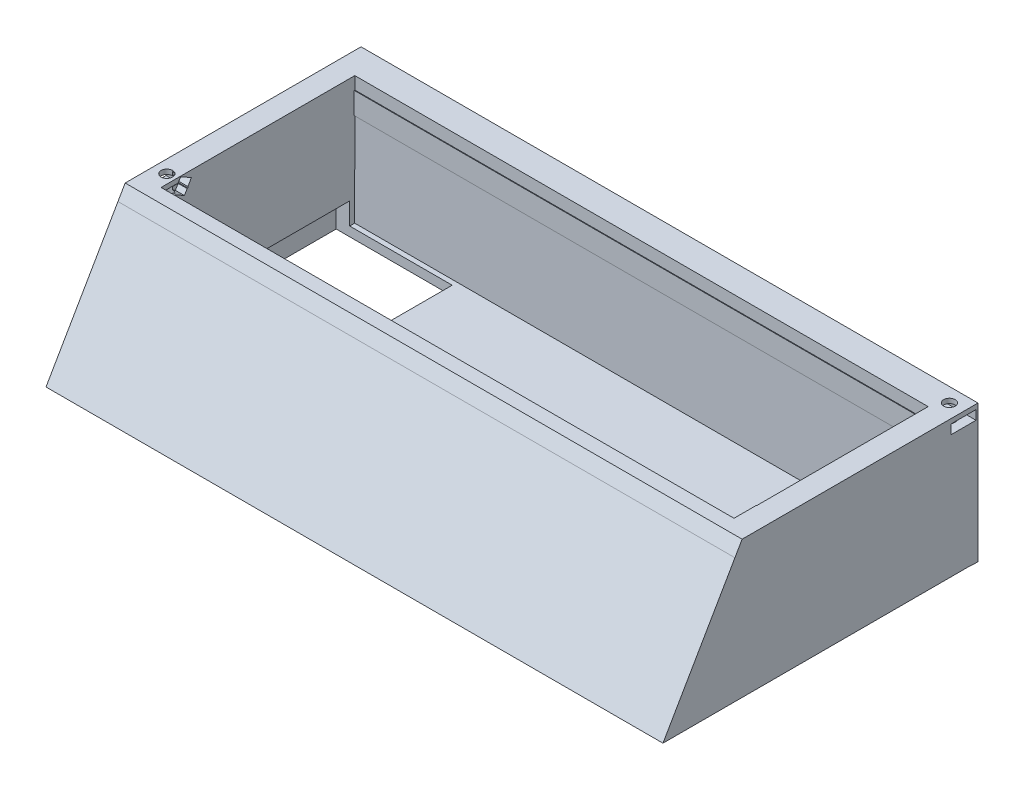
SolidWorks part; units mm, degrees
ref_plane "Alzado" through (0, 0, 0) normal (0, 0, 1) x (1, 0, 0)
ref_plane "Planta" through (0, 0, 0) normal (0, 1, 0) x (1, 0, 0)
ref_plane "Vista lateral" through (0, 0, 0) normal (1, 0, 0) x (0, 0, -1)
sketch "Sketch1" plane through (0, 0, 0) normal (1, 0, 0) x (0, 0, -1)
  line L0 (22.1085, 0) -> (32.4418, 17.8992)
  line L3 (-73.8644, -51.971) -> (121.1356, -51.9647) construction
  line L4 (22.1085, 0) -> (121.18, 0)
  line L5 (121.18, 0) -> (121.2142, 40)
  line L6 (45.2007, 40) -> (121.2142, 40)
  line L7 (32.4418, 17.8992) -> (45.2007, 40)
  line L8 (121.1416, -44.9647) -> (121.18, 0) construction
  dimension "D1" = 120
  dimension "D2" = 40
  dimension "D3" = 120
  dimension "D4" = 76.0135
extrude "Boss-Extrude1" add sketch "Sketch1" along normal blind 198
shell "Shell1" thickness 7 removed face at (99, 0, -71.6442)
sketch "Sketch2" plane through (0, 0, 0) normal (-1, 0, 0) x (0, 0, 1)
  line L0 (-30.1912, 0) -> (-32.9749, 0)
  line L1 (-32.9749, 0) -> (-52.026, 33)
  line L2 (73.8644, -51.971) -> (-121.1356, -51.9647) construction
  line L3 (-52.026, 33) -> (-49.2423, 33)
  line L4 (-49.2423, 33) -> (-30.1912, 0)
  dimension "D1" = 120
extrude "Boss-Extrude2" add sketch "Sketch2" against normal blind 191
ref_plane "Plane1" through (99, 0, 0) normal (1, 0, 0) x (0, 0, -1)
sketch "Sketch6" plane through (0, -0.1036, -121.1799) normal (0, -0.0009, -1) x (-1, 0, 0)
  line L1 (-198, 40.1036) -> (0, 40.1036)
  line L2 (-198, 40.1036) -> (-198, 0)
  line L3 (-198, 0) -> (0, 0)
  line L4 (0, 40.1036) -> (0, 0)
extrude "Boss-Extrude4" add sketch "Sketch6" along normal blind 2
sketch "Sketch7" plane through (0, 0, 0) normal (-1, 0, 0) x (0, 0, 1)
  line L1 (-123.1877, 9.047) -> (-35.2379, 9.047)
  line L2 (-123.1877, 9.047) -> (-123.1877, 12.047)
  line L3 (-123.1877, 12.047) -> (-35.2379, 12.047)
  line L4 (-35.2379, 9.047) -> (-35.2379, 12.047)
  dimension "D1" = 3
  dimension "D2" = 87.9498
  dimension "D3" = 3
ref_plane "Plane3" through (0, -0.0976, -114.1799) normal (0, 0.0009, 1) x (1, 0, 0)
ref_plane "Plane4" through (0, -14.278, -24.7321) normal (0, -0.5, -0.866) x (-1, 0, 0)
ref_plane "Plane5" through (7, 0, 0) normal (1, 0, 0) x (0, 0, -1)
ref_plane "Plane6" through (191, 0, 0) normal (-1, 0, 0) x (0, 0, 1)
sketch "Sketch8" plane through (198, 0, 0) normal (1, 0, 0) x (0, 0, -1)
  line L0 (123.2142, 39.9983) -> (123.2142, 52.0483)
  line L1 (123.2142, 39.9983) -> (45.2007, 40)
  line L2 (45.2007, 40) -> (52.1572, 52.0483)
  line L3 (123.2142, 52.0483) -> (52.1572, 52.0483)
  dimension "D1" = 12.05
  dimension "D2" = 78.0135
extrude "Boss-Extrude6" add sketch "Sketch8" against normal blind 198
sketch "Sketch9" plane through (0, 40.001, -0.0009) normal (0, -1, 0) x (-1, 0, 0)
  line L0 (0, 52.156) -> (-198, 52.156) construction
  line L1 (-7, 114.2131) -> (-191, 114.2131)
  line L2 (-7, 114.2131) -> (-7, 59.156)
  line L3 (-7, 59.156) -> (-191, 59.156)
  line L4 (-191, 114.2131) -> (-191, 59.156)
  line L5 (0, 123.2131) -> (0, 52.156) construction
  line L6 (0, 123.2131) -> (-198, 123.2131) construction
  line L7 (-198, 123.2131) -> (-198, 52.156) construction
  dimension "D1" = 7
  dimension "D2" = 7
  dimension "D3" = 9
  dimension "D4" = 7
extrude "Cut-Extrude1" cut sketch "Sketch9" against normal blind 4
sketch "Sketch10" plane through (0, -14.278, -24.7321) normal (0, -0.5, -0.866) x (-1, 0, 0)
  line L1 (-195.105, 67.1286) -> (-4.105, 67.1286)
  line L2 (-195.105, 67.1286) -> (-195.105, 62.6734)
  line L3 (-195.105, 62.6734) -> (-4.105, 62.6734)
  line L4 (-4.105, 67.1286) -> (-4.105, 62.6734)
  dimension "D1" = 191
  dimension "D2" = 191
extrude "Cut-Extrude2" cut sketch "Sketch10" along normal blind 4
ref_plane "Plane7" through (0, 44.001, -0.001) normal (0, -1, 0) x (-1, 0, 0)
split "Split4" trim tools "Plane7" bodies to split 114 resulting bodies 121
sketch "Sketch11" plane through (0, 44.001, -0.001) normal (0, 1, 0) x (1, 0, 0)
  circle A0 centre (4.1226, 56.7722) radius 1.8459
  circle A1 centre (193.3782, 118.6596) radius 1.8365
extrude "Cut-Extrude3" cut sketch "Sketch11" against normal blind 10
sketch "Sketch13" plane through (0, 0, 0) normal (-1, 0, 0) x (0, 0, 1)
  line L0 (-47.5102, 43.9999) -> (-123.2142, 43.9983) construction
  line L1 (-60.6515, 42.4996) -> (-52.6515, 42.4998)
  line L2 (-60.6515, 42.4996) -> (-60.6515, 39.4996)
  line L3 (-60.6515, 39.4996) -> (-52.6515, 39.4998)
  line L4 (-52.6515, 42.4998) -> (-52.6515, 39.4998)
  dimension "D1" = 8
  dimension "D2" = 3
  dimension "D3" = 3
  dimension "D4" = 1.5
extrude "Cut-Extrude4" cut sketch "Sketch13" against normal blind 10
sketch "Sketch15" plane through (198, 0, 0) normal (1, 0, 0) x (0, 0, -1)
  line L1 (122.5785, 42.4983) -> (114.5785, 42.4985)
  line L2 (122.5785, 42.4983) -> (122.5785, 39.5153)
  line L3 (122.5785, 39.5153) -> (114.5785, 39.5153)
  line L4 (114.5785, 42.4985) -> (114.5785, 39.5153)
  line L6 (47.5102, 43.9999) -> (123.2142, 43.9983) construction
  dimension "D1" = 1.5
  dimension "D2" = 8
extrude "Cut-Extrude6" cut sketch "Sketch15" against normal blind 10
sketch "Sketch16" plane through (0, 33, 0) normal (0, -1, 0) x (-1, 0, 0)
  line L1 (-7, 52.026) -> (-190.8842, 52.026)
  line L2 (-7, 52.026) -> (-7, 114.0066)
  line L3 (-7, 114.0066) -> (-190.8842, 114.0066)
  line L4 (-190.8842, 52.026) -> (-190.8842, 114.0066)
extrude "Cut-Extrude7" cut sketch "Sketch16" against normal blind 15
sketch "Sketch17" plane through (191, 0, 0) normal (-1, 0, 0) x (0, 0, 1)
  line L1 (-118.3902, 0) -> (-28.102, 0)
  line L2 (-118.3902, 0) -> (-118.3902, 3)
  line L3 (-118.3902, 3) -> (-28.102, 3)
  line L4 (-28.102, 0) -> (-28.102, 3)
  dimension "D1" = 90.2882
  dimension "D2" = 90.2882
  dimension "D3" = 3
  dimension "D4" = 3
extrude "Boss-Extrude7" add sketch "Sketch17" along normal blind 184
sketch "Sketch18" plane through (0, 0, 0) normal (0, -1, 0) x (1, 0, 0)
  circle A0 centre (186.292, -44.8599) radius 1.585
  circle A1 centre (11.7059, -44.8771) radius 1.6321
  circle A2 centre (11.7059, -44.8771) radius 1.585 construction
  dimension "D1" = 3.17
  dimension "D2" = 0
extrude "Cut-Extrude8" cut sketch "Sketch18" against normal blind 10
sketch "Sketch19" plane through (0, 0, 0) normal (0, -1, 0) x (1, 0, 0)
  line L1 (39.8872, -50.3796) -> (2.6595, -50.3796)
  line L2 (39.8872, -50.3796) -> (39.8872, -112.5753)
  line L3 (39.8872, -112.5753) -> (2.6595, -112.5753)
  line L4 (2.6595, -50.3796) -> (2.6595, -112.5753)
extrude "Cut-Extrude9" cut sketch "Sketch19" against normal blind 10
mirror "Mirror1" about plane through (99, 0, 0) normal (1, 0, 0) of "Cut-Extrude9"
